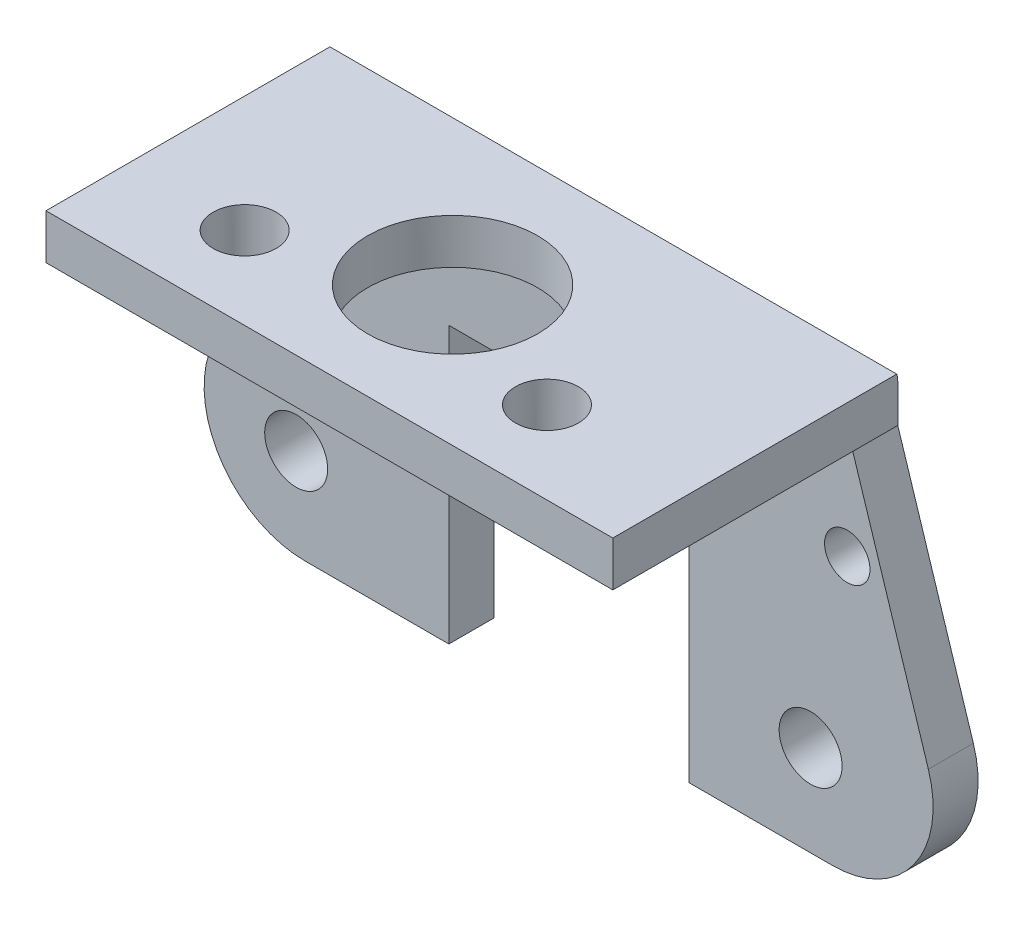
SolidWorks part; units mm, degrees
material "Alloy Steel"
ref_plane "Front Plane" through (0, 0, 0) normal (0, 0, 1) x (1, 0, 0)
ref_plane "Top Plane" through (0, 0, 0) normal (0, 1, 0) x (1, 0, 0)
ref_plane "Right Plane" through (0, 0, 0) normal (1, 0, 0) x (0, 0, -1)
ref_plane "Plane1" through (0, 0, 5) normal (0, 0, 1) x (1, 0, 0)
sketch "Sketch1" plane through (0, 0, 5) normal (0, 0, 1) x (1, 0, 0)
  line L0 (-21.23, 0) -> (-27.3364, -18.8061)
  line L1 (-19.7275, -29.2768) -> (22.1459, -29.2768)
  line L2 (29.7692, -18.8507) -> (23.77, 0)
  line L3 (23.77, 0) -> (23.77, 5)
  line L4 (23.77, 5) -> (-21.23, 5)
  line L5 (-21.23, 5) -> (-21.23, 0)
  arc A0 (-27.3364, -18.8061) -> (-19.7275, -29.2768) centre (-19.7275, -21.2768) ccw
  arc A1 (22.1459, -29.2768) -> (29.7692, -18.8507) centre (22.1459, -21.2768) ccw
extrude "Boss-Extrude1" add sketch "Sketch1" against normal blind 3.5719
sketch "Sketch2" plane through (0, 0, 5) normal (0, 0, 1) x (1, 0, 0)
  line L0 (23.77, 0) -> (-21.23, 0)
  line L1 (-21.23, 0) -> (-21.23, 3.5719)
  line L2 (-21.23, 3.5719) -> (23.77, 3.5719)
  line L3 (23.77, 3.5719) -> (23.77, 0)
  dimension "D1" = 3.5719
extrude "Boss-Extrude2" add sketch "Sketch2" along normal blind 19.05
hole_wizard "Ø5.0 (5) Diameter Hole1" positions "Sketch4" profile "Sketch3" hole size "Ø5.0" standard "ANSI Metric"
sketch "Sketch4" plane through (0, 0, 1.4281) normal (0, 0, -1) x (-1, 0, 0)
  point P0 (-20.42, -22.057)
  point P1 (20.42, -22.057)
sketch "Sketch3" plane through (20.42, -22.057, 1.4281) normal (1, 0, 0) x (0, 1, 0)
  line L0 (0, 0) -> (0, 22.6219)
  line L1 (0, 22.6219) -> (2.5, 22.6219)
  line L2 (2.5, 22.6219) -> (2.5, 0)
  line L5 (2.5, 0) -> (0, 0)
  line L11 (0, -6.35) -> (0, 107.95) construction
  dimension "Thru Hole Dia." = 5
  dimension "Thru Hole Depth" = 22.6219
fillet "Fillet1" radius 2 1 edges at (1.27, 5, 1.4281) tangent propagation no
fillet "Fillet2" [suppressed] radius 8 tangent propagation no
hole_wizard "Ø13.5 (13.5) Diameter Hole1" positions "Sketch6" profile "Sketch5" hole size "Ø13.5" standard "ANSI Metric"
sketch "Sketch6" plane through (0, 5, 0) normal (0, 1, 0) x (1, 0, 0)
  line L0 (-55, -5) -> (55, -5) construction
  point P0 (0, -13)
  dimension "D1" = 8
sketch "Sketch5" plane through (0, 5, 13) normal (1, 0, 0) x (0, 0, 1)
  line L0 (0, 0) -> (0, 34.2768)
  line L1 (0, 34.2768) -> (6.75, 34.2768)
  line L2 (6.75, 34.2768) -> (6.75, 0)
  line L5 (6.75, 0) -> (0, 0)
  line L11 (0, -6.35) -> (0, 107.95) construction
  dimension "Thru Hole Dia." = 13.5
  dimension "Thru Hole Depth" = 34.2768
hole_wizard "Ø5.0 (5) Diameter Hole2" positions "Sketch8" profile "Sketch7" hole size "Ø5.0" standard "ANSI Metric"
sketch "Sketch8" plane through (0, 5, 0) normal (0, 1, 0) x (1, 0, 0)
  line L0 (-55, -5) -> (55, -5) construction
  point P0 (-12, -17.51)
  point P1 (12, -17.51)
  dimension "D1" = 12.51
  dimension "D2" = 12.51
  dimension "D3" = 12
  dimension "D4" = 24
sketch "Sketch7" plane through (-12, 5, 17.51) normal (1, 0, 0) x (0, 0, 1)
  line L0 (0, 0) -> (0, 34.2768)
  line L1 (0, 34.2768) -> (2.5, 34.2768)
  line L2 (2.5, 34.2768) -> (2.5, 0)
  line L5 (2.5, 0) -> (0, 0)
  line L11 (0, -6.35) -> (0, 107.95) construction
  dimension "Thru Hole Dia." = 5
  dimension "Thru Hole Depth" = 34.2768
sketch "Sketch9" plane through (0, 0, 5) normal (0, 0, 1) x (1, 0, 0)
  line L1 (-21.23, 3.5719) -> (23.77, 3.5719)
  line L2 (-21.23, 3.5719) -> (-21.23, 5)
  line L3 (-21.23, 5) -> (23.77, 5)
  line L4 (23.77, 3.5719) -> (23.77, 5)
extrude "Cut-Extrude1" cut sketch "Sketch9" against normal blind 10
sketch "Sketch10" plane through (0, 0, 5) normal (0, 0, 1) x (1, 0, 0)
  circle A0 centre (23.3301, -7.4351) radius 1.8034
  circle A1 centre (-20.8887, -7.4351) radius 1.8034
  dimension "D1" = 3.6068
  dimension "D2" = 3.6068
extrude "Cut-Extrude2" cut sketch "Sketch10" against normal through all
sketch "Sketch11" plane through (0, 0, 5) normal (0, 0, 1) x (1, 0, 0)
  line L0 (-19.7275, -29.2768) -> (22.1459, -29.2768) construction
  line L1 (-8.2975, -29.2768) -> (10.7525, -29.2768)
  line L2 (-8.2975, -29.2768) -> (-8.2975, -7.3607)
  line L3 (-8.2975, -7.3607) -> (10.7525, -7.3607)
  line L4 (10.7525, -29.2768) -> (10.7525, -7.3607)
  dimension "D1" = 19.05
  dimension "D2" = 11.43
extrude "Cut-Extrude3" cut sketch "Sketch11" against normal through all
